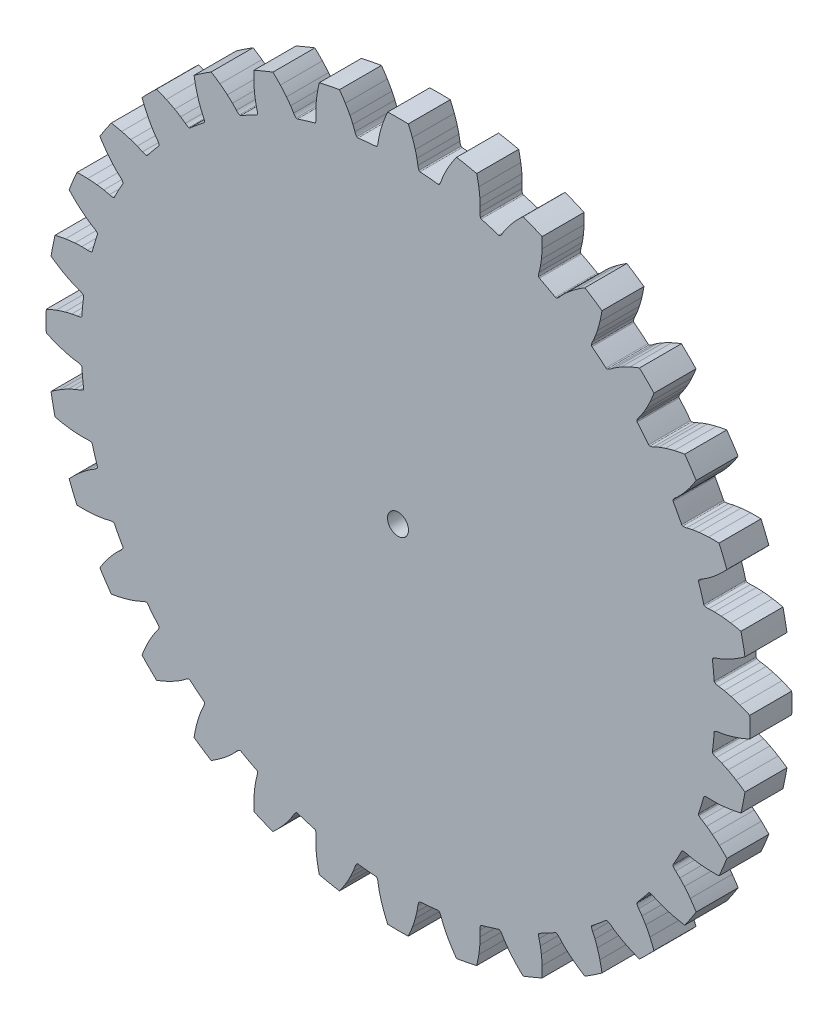
SolidWorks part; units mm, degrees
ref_plane "Front Plane" through (0, 0, 0) normal (0, 0, 1) x (1, 0, 0)
ref_plane "Top Plane" through (0, 0, 0) normal (0, 1, 0) x (1, 0, 0)
ref_plane "Right Plane" through (0, 0, 0) normal (1, 0, 0) x (0, 0, -1)
sketch "Model" plane through (0, 0, 0) normal (0, 0, 1) x (1, 0, 0)
  arc A1 (47.6887, -4.6969) -> (47.803, -3.3385) centre (0, 0) ccw
  arc A2 (47.9144, -3.1714) -> (47.803, -3.3385) centre (48.0052, -3.3526) ccw
  arc A3 (48.4758, -3.0015) -> (47.9144, -3.1714) centre (48.6888, -4.7173) ccw
  arc A4 (48.4758, -3.0015) -> (49.3301, -2.859) centre (47.1969, 7.2969) ccw
  arc A5 (49.3301, -2.859) -> (50.3502, -2.6078) centre (46.1914, 12.0843) ccw
  arc A6 (50.3502, -2.6078) -> (51.6994, -2.1663) centre (45.5635, 14.3022) ccw
  arc A7 (51.6994, -2.1663) -> (53.1817, -1.5528) centre (43.8651, 18.8607) ccw
  arc A8 (53.1817, -1.5528) -> (53.1817, 1.5528) centre (0, 0) ccw
  arc A9 (53.1817, 1.5528) -> (51.6994, 2.1663) centre (43.8651, -18.8607) ccw
  arc A10 (51.6994, 2.1663) -> (50.3502, 2.6078) centre (45.5635, -14.3022) ccw
  arc A11 (50.3502, 2.6078) -> (49.3301, 2.859) centre (46.1914, -12.0843) ccw
  arc A12 (49.3301, 2.859) -> (48.4758, 3.0015) centre (47.1969, -7.2969) ccw
  arc A13 (47.9144, 3.1714) -> (48.4758, 3.0015) centre (48.6888, 4.7173) ccw
  arc A14 (47.803, 3.3385) -> (47.9144, 3.1714) centre (48.0052, 3.3526) ccw
  arc A15 (47.803, 3.3385) -> (47.5358, 6.0515) centre (0, 0) ccw
  arc A16 (47.6124, 6.2371) -> (47.5358, 6.0515) centre (47.7368, 6.0771) ccw
  arc A17 (48.1299, 6.5133) -> (47.6124, 6.2371) centre (48.6736, 4.872) ccw
  arc A18 (48.1299, 6.5133) -> (48.94, 6.8198) centre (44.8665, 16.3643) ccw
  arc A19 (48.94, 6.8198) -> (49.8915, 7.2652) centre (42.9463, 20.8636) ccw
  arc A20 (49.8915, 7.2652) -> (51.1287, 7.9614) centre (41.8978, 22.9164) ccw
  arc A21 (51.1287, 7.9614) -> (52.4627, 8.8522) centre (39.3427, 27.056) ccw
  arc A22 (52.4627, 8.8522) -> (51.8568, 11.8982) centre (0, 0) ccw
  arc A23 (51.8568, 11.8982) -> (50.2834, 12.2107) centre (46.7018, -9.9407) ccw
  arc A24 (50.2834, 12.2107) -> (48.874, 12.3805) centre (47.4783, -5.1384) ccw
  arc A25 (48.874, 12.3805) -> (47.8244, 12.4279) centre (47.6613, -2.8406) ccw
  arc A26 (47.8244, 12.4279) -> (46.9587, 12.401) centre (47.7136, 2.051) ccw
  arc A27 (46.375, 12.4581) -> (46.9587, 12.401) centre (46.833, 14.1254) ccw
  arc A28 (46.2332, 12.6003) -> (46.375, 12.4581) centre (46.4287, 12.6536) ccw
  arc A29 (46.2332, 12.6003) -> (45.4418, 15.209) centre (0, 0) ccw
  arc A30 (45.4808, 15.406) -> (45.4418, 15.209) centre (45.634, 15.2733) ccw
  arc A31 (45.9344, 15.7779) -> (45.4808, 15.406) centre (46.7879, 14.2741) ccw
  arc A32 (45.9344, 15.7779) -> (46.6691, 16.2364) centre (40.8119, 24.8029) ccw
  arc A33 (46.6691, 16.2364) -> (47.5155, 16.8589) centre (38.0508, 28.8411) ccw
  arc A34 (47.5155, 16.8589) -> (48.5931, 17.7832) centre (36.622, 30.6499) ccw
  arc A35 (48.5931, 17.7832) -> (49.7277, 18.9171) centre (33.3084, 34.2115) ccw
  arc A36 (49.7277, 18.9171) -> (48.5392, 21.7864) centre (0, 0) ccw
  arc A37 (48.5392, 21.7864) -> (46.9351, 21.7859) centre (47.7438, -0.6386) ccw
  arc A38 (46.9351, 21.7859) -> (45.5196, 21.6775) centre (47.5684, 4.2229) ccw
  arc A39 (45.5196, 21.6775) -> (44.481, 21.5192) centre (47.2997, 6.5122) ccw
  arc A40 (44.481, 21.5192) -> (43.6371, 21.3239) centre (46.3967, 11.3201) ccw
  arc A41 (43.0535, 21.2661) -> (43.6371, 21.3239) centre (43.1774, 22.9907) ccw
  arc A42 (42.8866, 21.3778) -> (43.0535, 21.2661) centre (43.068, 21.4682) ccw
  arc A43 (42.8866, 21.3778) -> (41.6015, 23.782) centre (0, 0) ccw
  arc A44 (41.6013, 23.9828) -> (41.6015, 23.782) centre (41.7775, 23.8826) ccw
  arc A45 (41.9737, 24.436) -> (41.6013, 23.9828) centre (43.1041, 23.1277) ccw
  arc A46 (41.9737, 24.436) -> (42.6048, 25.0292) centre (35.1889, 32.2883) ccw
  arc A47 (42.6048, 25.0292) -> (43.3135, 25.8048) centre (31.693, 35.7103) ccw
  arc A48 (43.3135, 25.8048) -> (44.19, 26.9215) centre (29.9388, 37.2056) ccw
  arc A49 (44.19, 26.9215) -> (45.0816, 28.255) centre (25.994, 40.0523) ccw
  arc A50 (45.0816, 28.255) -> (43.3562, 30.8373) centre (0, 0) ccw
  arc A51 (43.3562, 30.8373) -> (41.783, 30.5239) centre (46.951, 8.688) ccw
  arc A52 (41.783, 30.5239) -> (40.4159, 30.1414) centre (45.8306, 13.4219) ccw
  arc A53 (40.4159, 30.1414) -> (39.4281, 29.7835) centre (45.1204, 15.6148) ccw
  arc A54 (39.4281, 29.7835) -> (38.6386, 29.4273) centre (43.2967, 20.1541) ccw
  arc A55 (38.0774, 29.2568) -> (38.6386, 29.4273) centre (37.8625, 30.9724) ccw
  arc A56 (37.892, 29.3338) -> (38.0774, 29.2568) centre (38.0522, 29.4579) ccw
  arc A57 (37.892, 29.3338) -> (36.1625, 31.4411) centre (0, 0) ccw
  arc A58 (36.1231, 31.638) -> (36.1625, 31.4411) centre (36.3154, 31.5741) ccw
  arc A59 (36.3999, 32.1552) -> (36.1231, 31.638) centre (37.7639, 31.0925) ccw
  arc A60 (36.3999, 32.1552) -> (36.9032, 32.86) centre (28.2136, 38.5329) ccw
  arc A61 (36.9032, 32.86) -> (37.447, 33.759) centre (24.1173, 41.2071) ccw
  arc A62 (37.447, 33.759) -> (38.0888, 35.0253) centre (22.1051, 42.3315) ccw
  arc A63 (38.0888, 35.0253) -> (38.7031, 36.5071) centre (17.6808, 44.3539) ccw
  arc A64 (38.7031, 36.5071) -> (36.5071, 38.7031) centre (0, 0) ccw
  arc A65 (36.5071, 38.7031) -> (35.0253, 38.0888) centre (44.3539, 17.6808) ccw
  arc A66 (35.0253, 38.0888) -> (33.759, 37.447) centre (42.3315, 22.1051) ccw
  arc A67 (33.759, 37.447) -> (32.86, 36.9032) centre (41.2071, 24.1173) ccw
  arc A68 (32.86, 36.9032) -> (32.1552, 36.3999) centre (38.5329, 28.2136) ccw
  arc A69 (31.638, 36.1231) -> (32.1552, 36.3999) centre (31.0925, 37.7639) ccw
  arc A70 (31.4411, 36.1625) -> (31.638, 36.1231) centre (31.5741, 36.3154) ccw
  arc A71 (31.4411, 36.1625) -> (29.3338, 37.892) centre (0, 0) ccw
  arc A72 (29.2568, 38.0774) -> (29.3338, 37.892) centre (29.4579, 38.0522) ccw
  arc A73 (29.4273, 38.6386) -> (29.2568, 38.0774) centre (30.9724, 37.8625) ccw
  arc A74 (29.4273, 38.6386) -> (29.7835, 39.4281) centre (20.1541, 43.2967) ccw
  arc A75 (29.7835, 39.4281) -> (30.1414, 40.4159) centre (15.6148, 45.1204) ccw
  arc A76 (30.1414, 40.4159) -> (30.5239, 41.783) centre (13.4219, 45.8306) ccw
  arc A77 (30.5239, 41.783) -> (30.8373, 43.3562) centre (8.688, 46.951) ccw
  arc A78 (30.8373, 43.3562) -> (28.255, 45.0816) centre (0, 0) ccw
  arc A79 (28.255, 45.0816) -> (26.9215, 44.19) centre (40.0523, 25.994) ccw
  arc A80 (26.9215, 44.19) -> (25.8048, 43.3135) centre (37.2056, 29.9388) ccw
  arc A81 (25.8048, 43.3135) -> (25.0292, 42.6048) centre (35.7103, 31.693) ccw
  arc A82 (25.0292, 42.6048) -> (24.436, 41.9737) centre (32.2883, 35.1889) ccw
  arc A83 (23.9828, 41.6013) -> (24.436, 41.9737) centre (23.1277, 43.1041) ccw
  arc A84 (23.782, 41.6015) -> (23.9828, 41.6013) centre (23.8826, 41.7775) ccw
  arc A85 (23.782, 41.6015) -> (21.3778, 42.8866) centre (0, 0) ccw
  arc A86 (21.2661, 43.0535) -> (21.3778, 42.8866) centre (21.4682, 43.068) ccw
  arc A87 (21.3239, 43.6371) -> (21.2661, 43.0535) centre (22.9907, 43.1774) ccw
  arc A88 (21.3239, 43.6371) -> (21.5192, 44.481) centre (11.3201, 46.3967) ccw
  arc A89 (21.5192, 44.481) -> (21.6775, 45.5196) centre (6.5122, 47.2997) ccw
  arc A90 (21.6775, 45.5196) -> (21.7859, 46.9351) centre (4.2229, 47.5684) ccw
  arc A91 (21.7859, 46.9351) -> (21.7864, 48.5392) centre (-0.6386, 47.7438) ccw
  arc A92 (21.7864, 48.5392) -> (18.9171, 49.7277) centre (0, 0) ccw
  arc A93 (18.9171, 49.7277) -> (17.7832, 48.5931) centre (34.2115, 33.3084) ccw
  arc A94 (17.7832, 48.5931) -> (16.8589, 47.5155) centre (30.6499, 36.622) ccw
  arc A95 (16.8589, 47.5155) -> (16.2364, 46.6691) centre (28.8411, 38.0508) ccw
  arc A96 (16.2364, 46.6691) -> (15.7779, 45.9344) centre (24.8029, 40.8119) ccw
  arc A97 (15.406, 45.4808) -> (15.7779, 45.9344) centre (14.2741, 46.7879) ccw
  arc A98 (15.209, 45.4418) -> (15.406, 45.4808) centre (15.2733, 45.634) ccw
  arc A99 (15.209, 45.4418) -> (12.6003, 46.2332) centre (0, 0) ccw
  arc A100 (12.4581, 46.375) -> (12.6003, 46.2332) centre (12.6536, 46.4287) ccw
  arc A101 (12.401, 46.9587) -> (12.4581, 46.375) centre (14.1254, 46.833) ccw
  arc A102 (12.401, 46.9587) -> (12.4279, 47.8244) centre (2.051, 47.7136) ccw
  arc A103 (12.4279, 47.8244) -> (12.3805, 48.874) centre (-2.8406, 47.6613) ccw
  arc A104 (12.3805, 48.874) -> (12.2107, 50.2834) centre (-5.1384, 47.4783) ccw
  arc A105 (12.2107, 50.2834) -> (11.8982, 51.8568) centre (-9.9407, 46.7018) ccw
  arc A106 (11.8982, 51.8568) -> (8.8522, 52.4627) centre (0, 0) ccw
  arc A107 (8.8522, 52.4627) -> (7.9614, 51.1287) centre (27.056, 39.3427) ccw
  arc A108 (7.9614, 51.1287) -> (7.2652, 49.8915) centre (22.9164, 41.8978) ccw
  arc A109 (7.2652, 49.8915) -> (6.8198, 48.94) centre (20.8636, 42.9463) ccw
  arc A110 (6.8198, 48.94) -> (6.5133, 48.1299) centre (16.3643, 44.8665) ccw
  arc A111 (6.2371, 47.6124) -> (6.5133, 48.1299) centre (4.872, 48.6736) ccw
  arc A112 (6.0515, 47.5358) -> (6.2371, 47.6124) centre (6.0771, 47.7368) ccw
  arc A113 (6.0515, 47.5358) -> (3.3385, 47.803) centre (0, 0) ccw
  arc A114 (3.1714, 47.9144) -> (3.3385, 47.803) centre (3.3526, 48.0052) ccw
  arc A115 (3.0015, 48.4758) -> (3.1714, 47.9144) centre (4.7173, 48.6888) ccw
  arc A116 (3.0015, 48.4758) -> (2.859, 49.3301) centre (-7.2969, 47.1969) ccw
  arc A117 (2.859, 49.3301) -> (2.6078, 50.3502) centre (-12.0843, 46.1914) ccw
  arc A118 (2.6078, 50.3502) -> (2.1663, 51.6994) centre (-14.3022, 45.5635) ccw
  arc A119 (2.1663, 51.6994) -> (1.5528, 53.1817) centre (-18.8607, 43.8651) ccw
  arc A120 (1.5528, 53.1817) -> (-1.5528, 53.1817) centre (0, 0) ccw
  arc A121 (-1.5528, 53.1817) -> (-2.1663, 51.6994) centre (18.8607, 43.8651) ccw
  arc A122 (-2.1663, 51.6994) -> (-2.6078, 50.3502) centre (14.3022, 45.5635) ccw
  arc A123 (-2.6078, 50.3502) -> (-2.859, 49.3301) centre (12.0843, 46.1914) ccw
  arc A124 (-2.859, 49.3301) -> (-3.0015, 48.4758) centre (7.2969, 47.1969) ccw
  arc A125 (-3.1714, 47.9144) -> (-3.0015, 48.4758) centre (-4.7173, 48.6888) ccw
  arc A126 (-3.3385, 47.803) -> (-3.1714, 47.9144) centre (-3.3526, 48.0052) ccw
  arc A127 (-3.3385, 47.803) -> (-6.0515, 47.5358) centre (0, 0) ccw
  arc A128 (-6.2371, 47.6124) -> (-6.0515, 47.5358) centre (-6.0771, 47.7368) ccw
  arc A129 (-6.5133, 48.1299) -> (-6.2371, 47.6124) centre (-4.872, 48.6736) ccw
  arc A130 (-6.5133, 48.1299) -> (-6.8198, 48.94) centre (-16.3643, 44.8665) ccw
  arc A131 (-6.8198, 48.94) -> (-7.2652, 49.8915) centre (-20.8636, 42.9463) ccw
  arc A132 (-7.2652, 49.8915) -> (-7.9614, 51.1287) centre (-22.9164, 41.8978) ccw
  arc A133 (-7.9614, 51.1287) -> (-8.8522, 52.4627) centre (-27.056, 39.3427) ccw
  arc A134 (-8.8522, 52.4627) -> (-11.8982, 51.8568) centre (0, 0) ccw
  arc A135 (-11.8982, 51.8568) -> (-12.2107, 50.2834) centre (9.9407, 46.7018) ccw
  arc A136 (-12.2107, 50.2834) -> (-12.3805, 48.874) centre (5.1384, 47.4783) ccw
  arc A137 (-12.3805, 48.874) -> (-12.4279, 47.8244) centre (2.8406, 47.6613) ccw
  arc A138 (-12.4279, 47.8244) -> (-12.401, 46.9587) centre (-2.051, 47.7136) ccw
  arc A139 (-12.4581, 46.375) -> (-12.401, 46.9587) centre (-14.1254, 46.833) ccw
  arc A140 (-12.6003, 46.2332) -> (-12.4581, 46.375) centre (-12.6536, 46.4287) ccw
  arc A141 (-12.6003, 46.2332) -> (-15.209, 45.4418) centre (0, 0) ccw
  arc A142 (-15.406, 45.4808) -> (-15.209, 45.4418) centre (-15.2733, 45.634) ccw
  arc A143 (-15.7779, 45.9344) -> (-15.406, 45.4808) centre (-14.2741, 46.7879) ccw
  arc A144 (-15.7779, 45.9344) -> (-16.2364, 46.6691) centre (-24.8029, 40.8119) ccw
  arc A145 (-16.2364, 46.6691) -> (-16.8589, 47.5155) centre (-28.8411, 38.0508) ccw
  arc A146 (-16.8589, 47.5155) -> (-17.7832, 48.5931) centre (-30.6499, 36.622) ccw
  arc A147 (-17.7832, 48.5931) -> (-18.9171, 49.7277) centre (-34.2115, 33.3084) ccw
  arc A148 (-18.9171, 49.7277) -> (-21.7864, 48.5392) centre (0, 0) ccw
  arc A149 (-21.7864, 48.5392) -> (-21.7859, 46.9351) centre (0.6386, 47.7438) ccw
  arc A150 (-21.7859, 46.9351) -> (-21.6775, 45.5196) centre (-4.2229, 47.5684) ccw
  arc A151 (-21.6775, 45.5196) -> (-21.5192, 44.481) centre (-6.5122, 47.2997) ccw
  arc A152 (-21.5192, 44.481) -> (-21.3239, 43.6371) centre (-11.3201, 46.3967) ccw
  arc A153 (-21.2661, 43.0535) -> (-21.3239, 43.6371) centre (-22.9907, 43.1774) ccw
  arc A154 (-21.3778, 42.8866) -> (-21.2661, 43.0535) centre (-21.4682, 43.068) ccw
  arc A155 (-21.3778, 42.8866) -> (-23.782, 41.6015) centre (0, 0) ccw
  arc A156 (-23.9828, 41.6013) -> (-23.782, 41.6015) centre (-23.8826, 41.7775) ccw
  arc A157 (-24.436, 41.9737) -> (-23.9828, 41.6013) centre (-23.1277, 43.1041) ccw
  arc A158 (-24.436, 41.9737) -> (-25.0292, 42.6048) centre (-32.2883, 35.1889) ccw
  arc A159 (-25.0292, 42.6048) -> (-25.8048, 43.3135) centre (-35.7103, 31.693) ccw
  arc A160 (-25.8048, 43.3135) -> (-26.9215, 44.19) centre (-37.2056, 29.9388) ccw
  arc A161 (-26.9215, 44.19) -> (-28.255, 45.0816) centre (-40.0523, 25.994) ccw
  arc A162 (-28.255, 45.0816) -> (-30.8373, 43.3562) centre (0, 0) ccw
  arc A163 (-30.8373, 43.3562) -> (-30.5239, 41.783) centre (-8.688, 46.951) ccw
  arc A164 (-30.5239, 41.783) -> (-30.1414, 40.4159) centre (-13.4219, 45.8306) ccw
  arc A165 (-30.1414, 40.4159) -> (-29.7835, 39.4281) centre (-15.6148, 45.1204) ccw
  arc A166 (-29.7835, 39.4281) -> (-29.4273, 38.6386) centre (-20.1541, 43.2967) ccw
  arc A167 (-29.2568, 38.0774) -> (-29.4273, 38.6386) centre (-30.9724, 37.8625) ccw
  arc A168 (-29.3338, 37.892) -> (-29.2568, 38.0774) centre (-29.4579, 38.0522) ccw
  arc A169 (-29.3338, 37.892) -> (-31.4411, 36.1625) centre (0, 0) ccw
  arc A170 (-31.638, 36.1231) -> (-31.4411, 36.1625) centre (-31.5741, 36.3154) ccw
  arc A171 (-32.1552, 36.3999) -> (-31.638, 36.1231) centre (-31.0925, 37.7639) ccw
  arc A172 (-32.1552, 36.3999) -> (-32.86, 36.9032) centre (-38.5329, 28.2136) ccw
  arc A173 (-32.86, 36.9032) -> (-33.759, 37.447) centre (-41.2071, 24.1173) ccw
  arc A174 (-33.759, 37.447) -> (-35.0253, 38.0888) centre (-42.3315, 22.1051) ccw
  arc A175 (-35.0253, 38.0888) -> (-36.5071, 38.7031) centre (-44.3539, 17.6808) ccw
  arc A176 (-36.5071, 38.7031) -> (-38.7031, 36.5071) centre (0, 0) ccw
  arc A177 (-38.7031, 36.5071) -> (-38.0888, 35.0253) centre (-17.6808, 44.3539) ccw
  arc A178 (-38.0888, 35.0253) -> (-37.447, 33.759) centre (-22.1051, 42.3315) ccw
  arc A179 (-37.447, 33.759) -> (-36.9032, 32.86) centre (-24.1173, 41.2071) ccw
  arc A180 (-36.9032, 32.86) -> (-36.3999, 32.1552) centre (-28.2136, 38.5329) ccw
  arc A181 (-36.1231, 31.638) -> (-36.3999, 32.1552) centre (-37.7639, 31.0925) ccw
  arc A182 (-36.1625, 31.4411) -> (-36.1231, 31.638) centre (-36.3154, 31.5741) ccw
  arc A183 (-36.1625, 31.4411) -> (-37.892, 29.3338) centre (0, 0) ccw
  arc A184 (-38.0774, 29.2568) -> (-37.892, 29.3338) centre (-38.0522, 29.4579) ccw
  arc A185 (-38.6386, 29.4273) -> (-38.0774, 29.2568) centre (-37.8625, 30.9724) ccw
  arc A186 (-38.6386, 29.4273) -> (-39.4281, 29.7835) centre (-43.2967, 20.1541) ccw
  arc A187 (-39.4281, 29.7835) -> (-40.4159, 30.1414) centre (-45.1204, 15.6148) ccw
  arc A188 (-40.4159, 30.1414) -> (-41.783, 30.5239) centre (-45.8306, 13.4219) ccw
  arc A189 (-41.783, 30.5239) -> (-43.3562, 30.8373) centre (-46.951, 8.688) ccw
  arc A190 (-43.3562, 30.8373) -> (-45.0816, 28.255) centre (0, 0) ccw
  arc A191 (-45.0816, 28.255) -> (-44.19, 26.9215) centre (-25.994, 40.0523) ccw
  arc A192 (-44.19, 26.9215) -> (-43.3135, 25.8048) centre (-29.9388, 37.2056) ccw
  arc A193 (-43.3135, 25.8048) -> (-42.6048, 25.0292) centre (-31.693, 35.7103) ccw
  arc A194 (-42.6048, 25.0292) -> (-41.9737, 24.436) centre (-35.1889, 32.2883) ccw
  arc A195 (-41.6013, 23.9828) -> (-41.9737, 24.436) centre (-43.1041, 23.1277) ccw
  arc A196 (-41.6015, 23.782) -> (-41.6013, 23.9828) centre (-41.7775, 23.8826) ccw
  arc A197 (-41.6015, 23.782) -> (-42.8866, 21.3778) centre (0, 0) ccw
  arc A198 (-43.0535, 21.2661) -> (-42.8866, 21.3778) centre (-43.068, 21.4682) ccw
  arc A199 (-43.6371, 21.3239) -> (-43.0535, 21.2661) centre (-43.1774, 22.9907) ccw
  arc A200 (-43.6371, 21.3239) -> (-44.481, 21.5192) centre (-46.3967, 11.3201) ccw
  arc A201 (-44.481, 21.5192) -> (-45.5196, 21.6775) centre (-47.2997, 6.5122) ccw
  arc A202 (-45.5196, 21.6775) -> (-46.9351, 21.7859) centre (-47.5684, 4.2229) ccw
  arc A203 (-46.9351, 21.7859) -> (-48.5392, 21.7864) centre (-47.7438, -0.6386) ccw
  arc A204 (-48.5392, 21.7864) -> (-49.7277, 18.9171) centre (0, 0) ccw
  arc A205 (-49.7277, 18.9171) -> (-48.5931, 17.7832) centre (-33.3084, 34.2115) ccw
  arc A206 (-48.5931, 17.7832) -> (-47.5155, 16.8589) centre (-36.622, 30.6499) ccw
  arc A207 (-47.5155, 16.8589) -> (-46.6691, 16.2364) centre (-38.0508, 28.8411) ccw
  arc A208 (-46.6691, 16.2364) -> (-45.9344, 15.7779) centre (-40.8119, 24.8029) ccw
  arc A209 (-45.4808, 15.406) -> (-45.9344, 15.7779) centre (-46.7879, 14.2741) ccw
  arc A210 (-45.4418, 15.209) -> (-45.4808, 15.406) centre (-45.634, 15.2733) ccw
  arc A211 (-45.4418, 15.209) -> (-46.2332, 12.6003) centre (0, 0) ccw
  arc A212 (-46.375, 12.4581) -> (-46.2332, 12.6003) centre (-46.4287, 12.6536) ccw
  arc A213 (-46.9587, 12.401) -> (-46.375, 12.4581) centre (-46.833, 14.1254) ccw
  arc A214 (-46.9587, 12.401) -> (-47.8244, 12.4279) centre (-47.7136, 2.051) ccw
  arc A215 (-47.8244, 12.4279) -> (-48.874, 12.3805) centre (-47.6613, -2.8406) ccw
  arc A216 (-48.874, 12.3805) -> (-50.2834, 12.2107) centre (-47.4783, -5.1384) ccw
  arc A217 (-50.2834, 12.2107) -> (-51.8568, 11.8982) centre (-46.7018, -9.9407) ccw
  arc A218 (-51.8568, 11.8982) -> (-52.4627, 8.8522) centre (0, 0) ccw
  arc A219 (-52.4627, 8.8522) -> (-51.1287, 7.9614) centre (-39.3427, 27.056) ccw
  arc A220 (-51.1287, 7.9614) -> (-49.8915, 7.2652) centre (-41.8978, 22.9164) ccw
  arc A221 (-49.8915, 7.2652) -> (-48.94, 6.8198) centre (-42.9463, 20.8636) ccw
  arc A222 (-48.94, 6.8198) -> (-48.1299, 6.5133) centre (-44.8665, 16.3643) ccw
  arc A223 (-47.6124, 6.2371) -> (-48.1299, 6.5133) centre (-48.6736, 4.872) ccw
  arc A224 (-47.5358, 6.0515) -> (-47.6124, 6.2371) centre (-47.7368, 6.0771) ccw
  arc A225 (-47.5358, 6.0515) -> (-47.803, 3.3385) centre (0, 0) ccw
  arc A226 (-47.9144, 3.1714) -> (-47.803, 3.3385) centre (-48.0052, 3.3526) ccw
  arc A227 (-48.4758, 3.0015) -> (-47.9144, 3.1714) centre (-48.6888, 4.7173) ccw
  arc A228 (-48.4758, 3.0015) -> (-49.3301, 2.859) centre (-47.1969, -7.2969) ccw
  arc A229 (-49.3301, 2.859) -> (-50.3502, 2.6078) centre (-46.1914, -12.0843) ccw
  arc A230 (-50.3502, 2.6078) -> (-51.6994, 2.1663) centre (-45.5635, -14.3022) ccw
  arc A231 (-51.6994, 2.1663) -> (-53.1817, 1.5528) centre (-43.8651, -18.8607) ccw
  arc A232 (-53.1817, 1.5528) -> (-53.1817, -1.5528) centre (0, 0) ccw
  arc A233 (-53.1817, -1.5528) -> (-51.6994, -2.1663) centre (-43.8651, 18.8607) ccw
  arc A234 (-51.6994, -2.1663) -> (-50.3502, -2.6078) centre (-45.5635, 14.3022) ccw
  arc A235 (-50.3502, -2.6078) -> (-49.3301, -2.859) centre (-46.1914, 12.0843) ccw
  arc A236 (-49.3301, -2.859) -> (-48.4758, -3.0015) centre (-47.1969, 7.2969) ccw
  arc A237 (-47.9144, -3.1714) -> (-48.4758, -3.0015) centre (-48.6888, -4.7173) ccw
  arc A238 (-47.803, -3.3385) -> (-47.9144, -3.1714) centre (-48.0052, -3.3526) ccw
  arc A239 (-47.803, -3.3385) -> (-47.5358, -6.0515) centre (0, 0) ccw
  arc A240 (-47.6124, -6.2371) -> (-47.5358, -6.0515) centre (-47.7368, -6.0771) ccw
  arc A241 (-48.1299, -6.5133) -> (-47.6124, -6.2371) centre (-48.6736, -4.872) ccw
  arc A242 (-48.1299, -6.5133) -> (-48.94, -6.8198) centre (-44.8665, -16.3643) ccw
  arc A243 (-48.94, -6.8198) -> (-49.8915, -7.2652) centre (-42.9463, -20.8636) ccw
  arc A244 (-49.8915, -7.2652) -> (-51.1287, -7.9614) centre (-41.8978, -22.9164) ccw
  arc A245 (-51.1287, -7.9614) -> (-52.4627, -8.8522) centre (-39.3427, -27.056) ccw
  arc A246 (-52.4627, -8.8522) -> (-51.8568, -11.8982) centre (0, 0) ccw
  arc A247 (-51.8568, -11.8982) -> (-50.2834, -12.2107) centre (-46.7018, 9.9407) ccw
  arc A248 (-50.2834, -12.2107) -> (-48.874, -12.3805) centre (-47.4783, 5.1384) ccw
  arc A249 (-48.874, -12.3805) -> (-47.8244, -12.4279) centre (-47.6613, 2.8406) ccw
  arc A250 (-47.8244, -12.4279) -> (-46.9587, -12.401) centre (-47.7136, -2.051) ccw
  arc A251 (-46.375, -12.4581) -> (-46.9587, -12.401) centre (-46.833, -14.1254) ccw
  arc A252 (-46.2332, -12.6003) -> (-46.375, -12.4581) centre (-46.4287, -12.6536) ccw
  arc A253 (-46.2332, -12.6003) -> (-45.4418, -15.209) centre (0, 0) ccw
  arc A254 (-45.4808, -15.406) -> (-45.4418, -15.209) centre (-45.634, -15.2733) ccw
  arc A255 (-45.9344, -15.7779) -> (-45.4808, -15.406) centre (-46.7879, -14.2741) ccw
  arc A256 (-45.9344, -15.7779) -> (-46.6691, -16.2364) centre (-40.8119, -24.8029) ccw
  arc A257 (-46.6691, -16.2364) -> (-47.5155, -16.8589) centre (-38.0508, -28.8411) ccw
  arc A258 (-47.5155, -16.8589) -> (-48.5931, -17.7832) centre (-36.622, -30.6499) ccw
  arc A259 (-48.5931, -17.7832) -> (-49.7277, -18.9171) centre (-33.3084, -34.2115) ccw
  arc A260 (-49.7277, -18.9171) -> (-48.5392, -21.7864) centre (0, 0) ccw
  arc A261 (-48.5392, -21.7864) -> (-46.9351, -21.7859) centre (-47.7438, 0.6386) ccw
  arc A262 (-46.9351, -21.7859) -> (-45.5196, -21.6775) centre (-47.5684, -4.2229) ccw
  arc A263 (-45.5196, -21.6775) -> (-44.481, -21.5192) centre (-47.2997, -6.5122) ccw
  arc A264 (-44.481, -21.5192) -> (-43.6371, -21.3239) centre (-46.3967, -11.3201) ccw
  arc A265 (-43.0535, -21.2661) -> (-43.6371, -21.3239) centre (-43.1774, -22.9907) ccw
  arc A266 (-42.8866, -21.3778) -> (-43.0535, -21.2661) centre (-43.068, -21.4682) ccw
  arc A267 (-42.8866, -21.3778) -> (-41.6015, -23.782) centre (0, 0) ccw
  arc A268 (-41.6013, -23.9828) -> (-41.6015, -23.782) centre (-41.7775, -23.8826) ccw
  arc A269 (-41.9737, -24.436) -> (-41.6013, -23.9828) centre (-43.1041, -23.1277) ccw
  arc A270 (-41.9737, -24.436) -> (-42.6048, -25.0292) centre (-35.1889, -32.2883) ccw
  arc A271 (-42.6048, -25.0292) -> (-43.3135, -25.8048) centre (-31.693, -35.7103) ccw
  arc A272 (-43.3135, -25.8048) -> (-44.19, -26.9215) centre (-29.9388, -37.2056) ccw
  arc A273 (-44.19, -26.9215) -> (-45.0816, -28.255) centre (-25.994, -40.0523) ccw
  arc A274 (-45.0816, -28.255) -> (-43.3562, -30.8373) centre (0, 0) ccw
  arc A275 (-43.3562, -30.8373) -> (-41.783, -30.5239) centre (-46.951, -8.688) ccw
  arc A276 (-41.783, -30.5239) -> (-40.4159, -30.1414) centre (-45.8306, -13.4219) ccw
  arc A277 (-40.4159, -30.1414) -> (-39.4281, -29.7835) centre (-45.1204, -15.6148) ccw
  arc A278 (-39.4281, -29.7835) -> (-38.6386, -29.4273) centre (-43.2967, -20.1541) ccw
  arc A279 (-38.0774, -29.2568) -> (-38.6386, -29.4273) centre (-37.8625, -30.9724) ccw
  arc A280 (-37.892, -29.3338) -> (-38.0774, -29.2568) centre (-38.0522, -29.4579) ccw
  arc A281 (-37.892, -29.3338) -> (-36.1625, -31.4411) centre (0, 0) ccw
  arc A282 (-36.1231, -31.638) -> (-36.1625, -31.4411) centre (-36.3154, -31.5741) ccw
  arc A283 (-36.3999, -32.1552) -> (-36.1231, -31.638) centre (-37.7639, -31.0925) ccw
  arc A284 (-36.3999, -32.1552) -> (-36.9032, -32.86) centre (-28.2136, -38.5329) ccw
  arc A285 (-36.9032, -32.86) -> (-37.447, -33.759) centre (-24.1173, -41.2071) ccw
  arc A286 (-37.447, -33.759) -> (-38.0888, -35.0253) centre (-22.1051, -42.3315) ccw
  arc A287 (-38.0888, -35.0253) -> (-38.7031, -36.5071) centre (-17.6808, -44.3539) ccw
  arc A288 (-38.7031, -36.5071) -> (-36.5071, -38.7031) centre (0, 0) ccw
  arc A289 (-36.5071, -38.7031) -> (-35.0253, -38.0888) centre (-44.3539, -17.6808) ccw
  arc A290 (-35.0253, -38.0888) -> (-33.759, -37.447) centre (-42.3315, -22.1051) ccw
  arc A291 (-33.759, -37.447) -> (-32.86, -36.9032) centre (-41.2071, -24.1173) ccw
  arc A292 (-32.86, -36.9032) -> (-32.1552, -36.3999) centre (-38.5329, -28.2136) ccw
  arc A293 (-31.638, -36.1231) -> (-32.1552, -36.3999) centre (-31.0925, -37.7639) ccw
  arc A294 (-31.4411, -36.1625) -> (-31.638, -36.1231) centre (-31.5741, -36.3154) ccw
  arc A295 (-31.4411, -36.1625) -> (-29.3338, -37.892) centre (0, 0) ccw
  arc A296 (-29.2568, -38.0774) -> (-29.3338, -37.892) centre (-29.4579, -38.0522) ccw
  arc A297 (-29.4273, -38.6386) -> (-29.2568, -38.0774) centre (-30.9724, -37.8625) ccw
  arc A298 (-29.4273, -38.6386) -> (-29.7835, -39.4281) centre (-20.1541, -43.2967) ccw
  arc A299 (-29.7835, -39.4281) -> (-30.1414, -40.4159) centre (-15.6148, -45.1204) ccw
  arc A300 (-30.1414, -40.4159) -> (-30.5239, -41.783) centre (-13.4219, -45.8306) ccw
  arc A301 (-30.5239, -41.783) -> (-30.8373, -43.3562) centre (-8.688, -46.951) ccw
  arc A302 (-30.8373, -43.3562) -> (-28.255, -45.0816) centre (0, 0) ccw
  arc A303 (-28.255, -45.0816) -> (-26.9215, -44.19) centre (-40.0523, -25.994) ccw
  arc A304 (-26.9215, -44.19) -> (-25.8048, -43.3135) centre (-37.2056, -29.9388) ccw
  arc A305 (-25.8048, -43.3135) -> (-25.0292, -42.6048) centre (-35.7103, -31.693) ccw
  arc A306 (-25.0292, -42.6048) -> (-24.436, -41.9737) centre (-32.2883, -35.1889) ccw
  arc A307 (-23.9828, -41.6013) -> (-24.436, -41.9737) centre (-23.1277, -43.1041) ccw
  arc A308 (-23.782, -41.6015) -> (-23.9828, -41.6013) centre (-23.8826, -41.7775) ccw
  arc A309 (-23.782, -41.6015) -> (-21.3778, -42.8866) centre (0, 0) ccw
  arc A310 (-21.2661, -43.0535) -> (-21.3778, -42.8866) centre (-21.4682, -43.068) ccw
  arc A311 (-21.3239, -43.6371) -> (-21.2661, -43.0535) centre (-22.9907, -43.1774) ccw
  arc A312 (-21.3239, -43.6371) -> (-21.5192, -44.481) centre (-11.3201, -46.3967) ccw
  arc A313 (-21.5192, -44.481) -> (-21.6775, -45.5196) centre (-6.5122, -47.2997) ccw
  arc A314 (-21.6775, -45.5196) -> (-21.7859, -46.9351) centre (-4.2229, -47.5684) ccw
  arc A315 (-21.7859, -46.9351) -> (-21.7864, -48.5392) centre (0.6386, -47.7438) ccw
  arc A316 (-21.7864, -48.5392) -> (-18.9171, -49.7277) centre (0, 0) ccw
  arc A317 (-18.9171, -49.7277) -> (-17.7832, -48.5931) centre (-34.2115, -33.3084) ccw
  arc A318 (-17.7832, -48.5931) -> (-16.8589, -47.5155) centre (-30.6499, -36.622) ccw
  arc A319 (-16.8589, -47.5155) -> (-16.2364, -46.6691) centre (-28.8411, -38.0508) ccw
  arc A320 (-16.2364, -46.6691) -> (-15.7779, -45.9344) centre (-24.8029, -40.8119) ccw
  arc A321 (-15.406, -45.4808) -> (-15.7779, -45.9344) centre (-14.2741, -46.7879) ccw
  arc A322 (-15.209, -45.4418) -> (-15.406, -45.4808) centre (-15.2733, -45.634) ccw
  arc A323 (-15.209, -45.4418) -> (-12.6003, -46.2332) centre (0, 0) ccw
  arc A324 (-12.4581, -46.375) -> (-12.6003, -46.2332) centre (-12.6536, -46.4287) ccw
  arc A325 (-12.401, -46.9587) -> (-12.4581, -46.375) centre (-14.1254, -46.833) ccw
  arc A326 (-12.401, -46.9587) -> (-12.4279, -47.8244) centre (-2.051, -47.7136) ccw
  arc A327 (-12.4279, -47.8244) -> (-12.3805, -48.874) centre (2.8406, -47.6613) ccw
  arc A328 (-12.3805, -48.874) -> (-12.2107, -50.2834) centre (5.1384, -47.4783) ccw
  arc A329 (-12.2107, -50.2834) -> (-11.8982, -51.8568) centre (9.9407, -46.7018) ccw
  arc A330 (-11.8982, -51.8568) -> (-8.8522, -52.4627) centre (0, 0) ccw
  arc A331 (-8.8522, -52.4627) -> (-7.9614, -51.1287) centre (-27.056, -39.3427) ccw
  arc A332 (-7.9614, -51.1287) -> (-7.2652, -49.8915) centre (-22.9164, -41.8978) ccw
  arc A333 (-7.2652, -49.8915) -> (-6.8198, -48.94) centre (-20.8636, -42.9463) ccw
  arc A334 (-6.8198, -48.94) -> (-6.5133, -48.1299) centre (-16.3643, -44.8665) ccw
  arc A335 (-6.2371, -47.6124) -> (-6.5133, -48.1299) centre (-4.872, -48.6736) ccw
  arc A336 (-6.0515, -47.5358) -> (-6.2371, -47.6124) centre (-6.0771, -47.7368) ccw
  arc A337 (-6.0515, -47.5358) -> (-3.3385, -47.803) centre (0, 0) ccw
  arc A338 (-3.1714, -47.9144) -> (-3.3385, -47.803) centre (-3.3526, -48.0052) ccw
  arc A339 (-3.0015, -48.4758) -> (-3.1714, -47.9144) centre (-4.7173, -48.6888) ccw
  arc A340 (-3.0015, -48.4758) -> (-2.859, -49.3301) centre (7.2969, -47.1969) ccw
  arc A341 (-2.859, -49.3301) -> (-2.6078, -50.3502) centre (12.0843, -46.1914) ccw
  arc A342 (-2.6078, -50.3502) -> (-2.1663, -51.6994) centre (14.3022, -45.5635) ccw
  arc A343 (-2.1663, -51.6994) -> (-1.5528, -53.1817) centre (18.8607, -43.8651) ccw
  arc A344 (-1.5528, -53.1817) -> (1.5528, -53.1817) centre (0, 0) ccw
  arc A345 (1.5528, -53.1817) -> (2.1663, -51.6994) centre (-18.8607, -43.8651) ccw
  arc A346 (2.1663, -51.6994) -> (2.6078, -50.3502) centre (-14.3022, -45.5635) ccw
  arc A347 (2.6078, -50.3502) -> (2.859, -49.3301) centre (-12.0843, -46.1914) ccw
  arc A348 (2.859, -49.3301) -> (3.0015, -48.4758) centre (-7.2969, -47.1969) ccw
  arc A349 (3.1714, -47.9144) -> (3.0015, -48.4758) centre (4.7173, -48.6888) ccw
  arc A350 (3.3385, -47.803) -> (3.1714, -47.9144) centre (3.3526, -48.0052) ccw
  arc A351 (3.3385, -47.803) -> (6.0515, -47.5358) centre (0, 0) ccw
  arc A352 (6.2371, -47.6124) -> (6.0515, -47.5358) centre (6.0771, -47.7368) ccw
  arc A353 (6.5133, -48.1299) -> (6.2371, -47.6124) centre (4.872, -48.6736) ccw
  arc A354 (6.5133, -48.1299) -> (6.8198, -48.94) centre (16.3643, -44.8665) ccw
  arc A355 (6.8198, -48.94) -> (7.2652, -49.8915) centre (20.8636, -42.9463) ccw
  arc A356 (7.2652, -49.8915) -> (7.9614, -51.1287) centre (22.9164, -41.8978) ccw
  arc A357 (7.9614, -51.1287) -> (8.8522, -52.4627) centre (27.056, -39.3427) ccw
  arc A358 (8.8522, -52.4627) -> (11.8982, -51.8568) centre (0, 0) ccw
  arc A359 (11.8982, -51.8568) -> (12.2107, -50.2834) centre (-9.9407, -46.7018) ccw
  arc A360 (12.2107, -50.2834) -> (12.3805, -48.874) centre (-5.1384, -47.4783) ccw
  arc A361 (12.3805, -48.874) -> (12.4279, -47.8244) centre (-2.8406, -47.6613) ccw
  arc A362 (12.4279, -47.8244) -> (12.401, -46.9587) centre (2.051, -47.7136) ccw
  arc A363 (12.4581, -46.375) -> (12.401, -46.9587) centre (14.1254, -46.833) ccw
  arc A364 (12.6003, -46.2332) -> (12.4581, -46.375) centre (12.6536, -46.4287) ccw
  arc A365 (12.6003, -46.2332) -> (15.209, -45.4418) centre (0, 0) ccw
  arc A366 (15.406, -45.4808) -> (15.209, -45.4418) centre (15.2733, -45.634) ccw
  arc A367 (15.7779, -45.9344) -> (15.406, -45.4808) centre (14.2741, -46.7879) ccw
  arc A368 (15.7779, -45.9344) -> (16.2364, -46.6691) centre (24.8029, -40.8119) ccw
  arc A369 (16.2364, -46.6691) -> (16.8589, -47.5155) centre (28.8411, -38.0508) ccw
  arc A370 (16.8589, -47.5155) -> (17.7832, -48.5931) centre (30.6499, -36.622) ccw
  arc A371 (17.7832, -48.5931) -> (18.9171, -49.7277) centre (34.2115, -33.3084) ccw
  arc A372 (18.9171, -49.7277) -> (21.7864, -48.5392) centre (0, 0) ccw
  arc A373 (21.7864, -48.5392) -> (21.7859, -46.9351) centre (-0.6386, -47.7438) ccw
  arc A374 (21.7859, -46.9351) -> (21.6775, -45.5196) centre (4.2229, -47.5684) ccw
  arc A375 (21.6775, -45.5196) -> (21.5192, -44.481) centre (6.5122, -47.2997) ccw
  arc A376 (21.5192, -44.481) -> (21.3239, -43.6371) centre (11.3201, -46.3967) ccw
  arc A377 (21.2661, -43.0535) -> (21.3239, -43.6371) centre (22.9907, -43.1774) ccw
  arc A378 (21.3778, -42.8866) -> (21.2661, -43.0535) centre (21.4682, -43.068) ccw
  arc A379 (21.3778, -42.8866) -> (23.782, -41.6015) centre (0, 0) ccw
  arc A380 (23.9828, -41.6013) -> (23.782, -41.6015) centre (23.8826, -41.7775) ccw
  arc A381 (24.436, -41.9737) -> (23.9828, -41.6013) centre (23.1277, -43.1041) ccw
  arc A382 (24.436, -41.9737) -> (25.0292, -42.6048) centre (32.2883, -35.1889) ccw
  arc A383 (25.0292, -42.6048) -> (25.8048, -43.3135) centre (35.7103, -31.693) ccw
  arc A384 (25.8048, -43.3135) -> (26.9215, -44.19) centre (37.2056, -29.9388) ccw
  arc A385 (26.9215, -44.19) -> (28.255, -45.0816) centre (40.0523, -25.994) ccw
  arc A386 (28.255, -45.0816) -> (30.8373, -43.3562) centre (0, 0) ccw
  arc A387 (30.8373, -43.3562) -> (30.5239, -41.783) centre (8.688, -46.951) ccw
  arc A388 (30.5239, -41.783) -> (30.1414, -40.4159) centre (13.4219, -45.8306) ccw
  arc A389 (30.1414, -40.4159) -> (29.7835, -39.4281) centre (15.6148, -45.1204) ccw
  arc A390 (29.7835, -39.4281) -> (29.4273, -38.6386) centre (20.1541, -43.2967) ccw
  arc A391 (29.2568, -38.0774) -> (29.4273, -38.6386) centre (30.9724, -37.8625) ccw
  arc A392 (29.3338, -37.892) -> (29.2568, -38.0774) centre (29.4579, -38.0522) ccw
  arc A393 (29.3338, -37.892) -> (31.4411, -36.1625) centre (0, 0) ccw
  arc A394 (31.638, -36.1231) -> (31.4411, -36.1625) centre (31.5741, -36.3154) ccw
  arc A395 (32.1552, -36.3999) -> (31.638, -36.1231) centre (31.0925, -37.7639) ccw
  arc A396 (32.1552, -36.3999) -> (32.86, -36.9032) centre (38.5329, -28.2136) ccw
  arc A397 (32.86, -36.9032) -> (33.759, -37.447) centre (41.2071, -24.1173) ccw
  arc A398 (33.759, -37.447) -> (35.0253, -38.0888) centre (42.3315, -22.1051) ccw
  arc A399 (35.0253, -38.0888) -> (36.5071, -38.7031) centre (44.3539, -17.6808) ccw
  arc A400 (36.5071, -38.7031) -> (38.7031, -36.5071) centre (0, 0) ccw
  arc A401 (38.7031, -36.5071) -> (38.0888, -35.0253) centre (17.6808, -44.3539) ccw
  arc A402 (38.0888, -35.0253) -> (37.447, -33.759) centre (22.1051, -42.3315) ccw
  arc A403 (37.447, -33.759) -> (36.9032, -32.86) centre (24.1173, -41.2071) ccw
  arc A404 (36.9032, -32.86) -> (36.3999, -32.1552) centre (28.2136, -38.5329) ccw
  arc A405 (36.1231, -31.638) -> (36.3999, -32.1552) centre (37.7639, -31.0925) ccw
  arc A406 (36.1625, -31.4411) -> (36.1231, -31.638) centre (36.3154, -31.5741) ccw
  arc A407 (36.1625, -31.4411) -> (37.892, -29.3338) centre (0, 0) ccw
  arc A408 (38.0774, -29.2568) -> (37.892, -29.3338) centre (38.0522, -29.4579) ccw
  arc A409 (38.6386, -29.4273) -> (38.0774, -29.2568) centre (37.8625, -30.9724) ccw
  arc A410 (38.6386, -29.4273) -> (39.4281, -29.7835) centre (43.2967, -20.1541) ccw
  arc A411 (39.4281, -29.7835) -> (40.4159, -30.1414) centre (45.1204, -15.6148) ccw
  arc A412 (40.4159, -30.1414) -> (41.783, -30.5239) centre (45.8306, -13.4219) ccw
  arc A413 (41.783, -30.5239) -> (43.3562, -30.8373) centre (46.951, -8.688) ccw
  arc A414 (43.3562, -30.8373) -> (45.0816, -28.255) centre (0, 0) ccw
  arc A415 (45.0816, -28.255) -> (44.19, -26.9215) centre (25.994, -40.0523) ccw
  arc A416 (44.19, -26.9215) -> (43.3135, -25.8048) centre (29.9388, -37.2056) ccw
  arc A417 (43.3135, -25.8048) -> (42.6048, -25.0292) centre (31.693, -35.7103) ccw
  arc A418 (42.6048, -25.0292) -> (41.9737, -24.436) centre (35.1889, -32.2883) ccw
  arc A419 (41.6013, -23.9828) -> (41.9737, -24.436) centre (43.1041, -23.1277) ccw
  arc A420 (41.6015, -23.782) -> (41.6013, -23.9828) centre (41.7775, -23.8826) ccw
  arc A421 (41.6015, -23.782) -> (42.8866, -21.3778) centre (0, 0) ccw
  arc A422 (43.0535, -21.2661) -> (42.8866, -21.3778) centre (43.068, -21.4682) ccw
  arc A423 (43.6371, -21.3239) -> (43.0535, -21.2661) centre (43.1774, -22.9907) ccw
  arc A424 (43.6371, -21.3239) -> (44.481, -21.5192) centre (46.3967, -11.3201) ccw
  arc A425 (44.481, -21.5192) -> (45.5196, -21.6775) centre (47.2997, -6.5122) ccw
  arc A426 (45.5196, -21.6775) -> (46.9351, -21.7859) centre (47.5684, -4.2229) ccw
  arc A427 (46.9351, -21.7859) -> (48.5392, -21.7864) centre (47.7438, 0.6386) ccw
  arc A428 (48.5392, -21.7864) -> (49.7277, -18.9171) centre (0, 0) ccw
  arc A429 (49.7277, -18.9171) -> (48.5931, -17.7832) centre (33.3084, -34.2115) ccw
  arc A430 (48.5931, -17.7832) -> (47.5155, -16.8589) centre (36.622, -30.6499) ccw
  arc A431 (47.5155, -16.8589) -> (46.6691, -16.2364) centre (38.0508, -28.8411) ccw
  arc A432 (46.6691, -16.2364) -> (45.9344, -15.7779) centre (40.8119, -24.8029) ccw
  arc A433 (45.4808, -15.406) -> (45.9344, -15.7779) centre (46.7879, -14.2741) ccw
  arc A434 (45.4418, -15.209) -> (45.4808, -15.406) centre (45.634, -15.2733) ccw
  arc A435 (45.4418, -15.209) -> (46.2332, -12.6003) centre (0, 0) ccw
  arc A436 (46.375, -12.4581) -> (46.2332, -12.6003) centre (46.4287, -12.6536) ccw
  arc A437 (46.9587, -12.401) -> (46.375, -12.4581) centre (46.833, -14.1254) ccw
  arc A438 (46.9587, -12.401) -> (47.8244, -12.4279) centre (47.7136, -2.051) ccw
  arc A439 (47.8244, -12.4279) -> (48.874, -12.3805) centre (47.6613, 2.8406) ccw
  arc A440 (48.874, -12.3805) -> (50.2834, -12.2107) centre (47.4783, 5.1384) ccw
  arc A441 (50.2834, -12.2107) -> (51.8568, -11.8982) centre (46.7018, 9.9407) ccw
  arc A442 (51.8568, -11.8982) -> (52.4627, -8.8522) centre (0, 0) ccw
  arc A443 (52.4627, -8.8522) -> (51.1287, -7.9614) centre (39.3427, -27.056) ccw
  arc A444 (51.1287, -7.9614) -> (49.8915, -7.2652) centre (41.8978, -22.9164) ccw
  arc A445 (49.8915, -7.2652) -> (48.94, -6.8198) centre (42.9463, -20.8636) ccw
  arc A446 (48.94, -6.8198) -> (48.1299, -6.5133) centre (44.8665, -16.3643) ccw
  arc A447 (47.6124, -6.2371) -> (48.1299, -6.5133) centre (48.6736, -4.872) ccw
  arc A448 (47.5358, -6.0515) -> (47.6124, -6.2371) centre (47.7368, -6.0771) ccw
  arc A449 (47.5358, -6.0515) -> (47.6887, -4.6969) centre (0, 0) ccw
extrude "Boss-Extrude1" add sketch "Model" along normal blind 6.35
sketch "Sketch2" plane through (0, 0, 6.35) normal (0, 0, 1) x (1, 0, 0)
  circle A0 centre (0, 0) radius 1.5875
  dimension "D1" = 3.175
extrude "Cut-Extrude1" cut sketch "Sketch2" against normal through all
